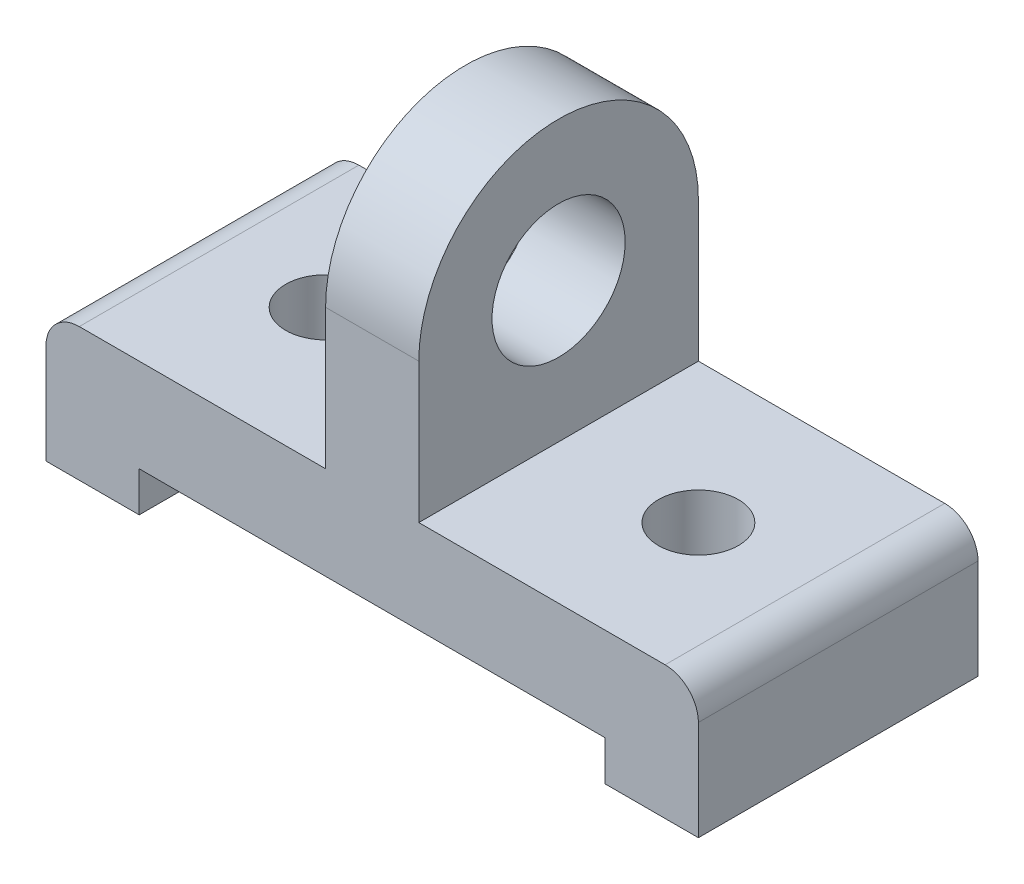
SolidWorks part; units mm, degrees
ref_plane "Front Plane" through (0, 0, 0) normal (0, 0, 1) x (1, 0, 0)
ref_plane "Top Plane" through (0, 0, 0) normal (0, 1, 0) x (1, 0, 0)
ref_plane "Right Plane" through (0, 0, 0) normal (1, 0, 0) x (0, 0, -1)
sketch "Sketch1" plane through (0, 0, 0) normal (0, 1, 0) x (1, 0, 0)
  line L0 (0, 0) -> (0, 420)
  line L1 (0, 420) -> (980, 420)
  line L2 (980, 420) -> (980, 0)
  line L3 (980, 0) -> (0, 0)
extrude "Boss-Extrude1" add sketch "Sketch1" along normal blind 200
sketch "Sketch2" plane through (0, 0, 0) normal (0, 0, 1) x (1, 0, 0)
  line L1 (0, 0) -> (980, 0) construction
  line L2 (140, 0) -> (140, 60)
  line L3 (140, 60) -> (840, 60)
  line L4 (840, 60) -> (840, 0)
  line L5 (840, 0) -> (140, 0)
extrude "Cut-Extrude1" cut sketch "Sketch2" against normal up to surface (420 mm away) contours L2 L3 L4 L5 up to face at (490, 100, -420)
sketch "Sketch3" plane through (0, 0, 0) normal (0, 0, 1) x (1, 0, 0)
  line L0 (420, 200) -> (560, 200)
  line L1 (0, 200) -> (980, 200) construction
  line L2 (420, 200) -> (420, 620)
  line L3 (420, 620) -> (560, 620)
  line L4 (560, 620) -> (560, 200)
extrude "Boss-Extrude2" add sketch "Sketch3" against normal up to surface (420 mm away) up to face at (490, 65, -420)
sketch "Sketch4" plane through (560, 0, 0) normal (1, 0, 0) x (0, 0, -1)
  circle A0 centre (210, 410) radius 100
extrude "Cut-Extrude2" cut sketch "Sketch4" against normal blind 200
sketch "Sketch5" plane through (0, 200, 0) normal (0, 1, 0) x (1, 0, 0)
  line L0 (490, 420) -> (490, 0) construction
  line L1 (420, 420) -> (560, 420) construction
  line L2 (560, 0) -> (420, 0) construction
  circle A0 centre (770, 210) radius 60
  circle A1 centre (210, 210) radius 60
extrude "Cut-Extrude3" cut sketch "Sketch5" against normal blind 200
fillet "Fillet1" 2 edges at (490, 620, 0) (490, 620, -420) type full round first side face at (490, 180, 0) second side face at (490, 180, -420) middle face at (490, 620, -210)
fillet "Fillet2" radius 50 1 edges at (980, 200, -210)
fillet "Fillet3" radius 50 1 edges at (0, 200, -210)
